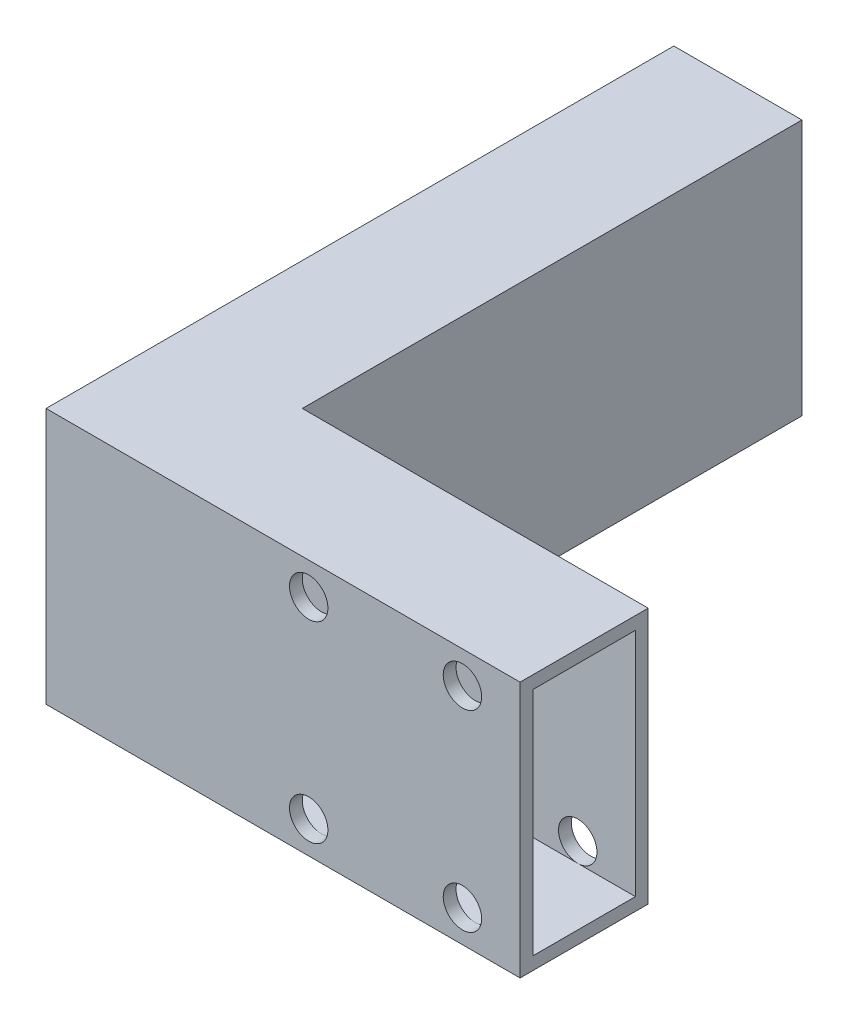
SolidWorks part; units mm, degrees
ref_plane "前视基准面" through (0, 0, 0) normal (0, 0, 1) x (1, 0, 0)
ref_plane "上视基准面" through (0, 0, 0) normal (0, 1, 0) x (1, 0, 0)
ref_plane "右视基准面" through (0, 0, 0) normal (1, 0, 0) x (0, 0, -1)
sketch "草图1" plane through (0, 0, 0) normal (0, 1, 0) x (1, 0, 0)
  line L0 (0, 0) -> (0, 35)
  line L1 (0, 35) -> (10, 35)
  line L2 (10, 35) -> (10, 10)
  line L3 (10, 10) -> (37, 10)
  line L4 (37, 10) -> (37, 0)
  line L5 (37, 0) -> (0, 0)
  dimension "D1" = 10
  dimension "D2" = 10
extrude "凸台-拉伸1" add sketch "草图1" along normal blind 20
sketch "草图2" plane through (0, 0, -10) normal (0, 0, -1) x (-1, 0, 0)
  line L0 (-37, 0) -> (-10, 20)
  line L1 (-37, 20) -> (-10, 20) construction
  line L2 (-10, 20) -> (-10, 0) construction
  line L3 (-20.5, 17.5) -> (-32.5, 17.5)
  line L4 (-20.5, 17.5) -> (-20.5, 2.5)
  line L5 (-32.5, 17.5) -> (-32.5, 2.5)
  line L6 (-20.5, 2.5) -> (-32.5, 2.5)
  line L7 (-20.5, 17.5) -> (-32.5, 2.5) construction
  line L8 (-32.5, 17.5) -> (-20.5, 2.5) construction
  line L9 (-37, 20) -> (-10, 0)
  line L10 (-37, 20) -> (-37, 0) construction
  point P8 (-26.5, 10)
  dimension "D1" = 12
  dimension "D2" = 15
  dimension "D3" = 4.5
hole_wizard "大小mm Press 暗销孔1" positions "3D草图1" profile "草图3" hole size "Ø3.0" standard "ANSI Metric" end condition through all
sketch3d "3D草图1"
  point P0 (20.5, 2.5, -10)
  point P3 (32.5, 2.5, -10)
  point P6 (32.5, 17.5, -10)
  point P9 (20.5, 17.5, -10)
sketch "草图3" plane through (20.5, 2.5, -10) normal (1, 0, 0) x (0, 1, 0)
  line L0 (0, 0) -> (0, 10)
  line L1 (0, 10) -> (1.5, 10)
  line L2 (1.5, 10) -> (1.5, 0)
  line L5 (1.5, 0) -> (0, 0)
  line L11 (0, -6.35) -> (0, 107.95) construction
  dimension "通孔孔直径" = 3
  dimension "通孔孔深度" = 10
sketch "草图4" plane through (0, 0, -35) normal (0, 0, -1) x (-1, 0, 0)
  line L0 (-9, 1) -> (-1, 1)
  line L1 (-1, 1) -> (-1, 19)
  line L2 (-1, 19) -> (-9, 19)
  line L3 (-9, 19) -> (-9, 1)
  line L4 (-10, 0) -> (0, 0)
  line L5 (0, 0) -> (0, 20)
  line L6 (0, 20) -> (-10, 20)
  line L7 (-10, 20) -> (-10, 0)
  line L8 (-10, 0) -> (0, 0)
  line L9 (0, 0) -> (0, 20)
  line L10 (0, 20) -> (-10, 20)
  line L11 (-10, 20) -> (-10, 0)
  dimension "D1" = 0
  dimension "D2" = 1
extrude "切除-拉伸1" cut sketch "草图4" against normal blind 34 contours L0 L1 L2 L3
sketch "草图5" plane through (37, 0, 0) normal (1, 0, 0) x (0, 0, -1)
  line L0 (1, 1) -> (9, 1)
  line L1 (9, 1) -> (9, 19)
  line L2 (9, 19) -> (1, 19)
  line L3 (1, 19) -> (1, 1)
  line L4 (0, 0) -> (10, 0)
  line L5 (10, 0) -> (10, 20)
  line L6 (10, 20) -> (0, 20)
  line L7 (0, 20) -> (0, 0)
  line L8 (0, 0) -> (10, 0)
  line L9 (10, 0) -> (10, 20)
  line L10 (10, 20) -> (0, 20)
  line L11 (0, 20) -> (0, 0)
  dimension "D1" = 0
  dimension "D2" = 1
extrude "切除-拉伸3" cut sketch "草图5" against normal blind 36 contours L1 L2 L3 L0
sketch "草图7" plane through (0, 0, -35) normal (0, 0, -1) x (-1, 0, 0)
  line L0 (0, 0) -> (-10, 0)
  line L1 (-10, 0) -> (-10, 20)
  line L2 (-10, 20) -> (0, 20)
  line L3 (0, 20) -> (0, 0)
  line L4 (-9, 1) -> (-1, 1)
  line L5 (-9, 19) -> (-9, 1)
  line L6 (-1, 19) -> (-9, 19)
  line L7 (-1, 1) -> (-1, 19)
  line L8 (-9, 1) -> (-1, 1)
  line L9 (-9, 19) -> (-9, 1)
  line L10 (-1, 19) -> (-9, 19)
  line L11 (-1, 1) -> (-1, 19)
  dimension "D1" = 0
extrude "凸台-拉伸2" add sketch "草图7" along normal blind 14
